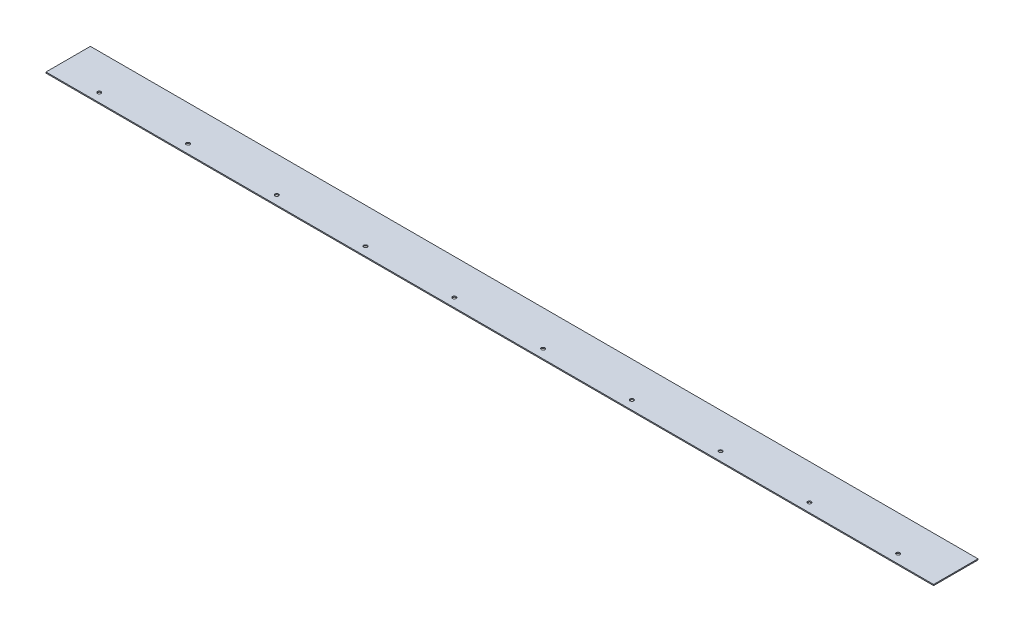
SolidWorks part; units mm, degrees
note: The reader was unsure of these and kept them because the rebuilt part matched: thickness of "Base-Flange1", "Sheet-Metal1", "Sheet-Metal2".
material "Galvanized Steel"
ref_plane "Front Plane" through (0, 0, 0) normal (0, 0, 1) x (1, 0, 0)
ref_plane "Top Plane" through (0, 0, 0) normal (0, 1, 0) x (1, 0, 0)
ref_plane "Right Plane" through (0, 0, 0) normal (1, 0, 0) x (0, 0, -1)
sketch "Sketch1" plane through (0, 0, 0) normal (0, 1, 0) x (1, 0, 0)
  line L1 (-500, -25) -> (500, -25)
  line L2 (-500, -25) -> (-500, 25)
  line L3 (-500, 25) -> (500, 25)
  line L4 (500, -25) -> (500, 25)
  line L5 (-500, -25) -> (500, 25) construction
  line L6 (-500, 25) -> (500, -25) construction
  point P0 (0, 0)
base flange "Base-Flange1" sketch "Sketch1" thickness 1.2 reverse thickness direction no parameters "D1"=2
sketch "Sketch2" plane through (0, 0, 0) normal (0, 1, 0) x (1, 0, 0)
  line L0 (-500, 25) -> (-500, -25) construction
  circle A0 centre (-450, -15) radius 2
  circle A1 centre (-350, -15) radius 2
  circle A2 centre (-250, -15) radius 2
  circle A3 centre (-150, -15) radius 2
  circle A4 centre (-50, -15) radius 2
  circle A5 centre (50, -15) radius 2
  circle A6 centre (150, -15) radius 2
  circle A7 centre (250, -15) radius 2
  circle A8 centre (350, -15) radius 2
  circle A9 centre (450, -15) radius 2
  dimension "D1" = 50
extrude "Cut-Extrude1" cut sketch "Sketch2" against normal blind 10
sketch "Bend-Lines1" [suppressed] plane through (0, 0, 0) normal (0, 1, 0) x (1, 0, 0)
sketch "Bounding-Box1" [suppressed] plane through (0, 0, 0) normal (0, 1, 0) x (1, 0, 0)
sheet metal parameters "Sheet-Metal1" thickness 1.2 parameters "D1"=2
flat pattern "Flat-Pattern1" [suppressed]
sketch "Bend-Lines2" plane through (0, 0, 0) normal (0, 1, 0) x (1, 0, 0)
sketch3d "Bounding-Box2" [suppressed]
  line L0 (-500, 25.75, 0) -> (500, 25.75, 0) construction
  line L1 (-500, -25.75, 0) -> (500, -25.75, 0) construction
  line L2 (-500, 25.75, 0) -> (-500, -25.75, 0) construction
  line L3 (500, 25.75, 0) -> (500, -25.75, 0) construction
sheet metal parameters "Sheet-Metal2" thickness 1.2 parameters "D1"=2, "D7"=0.5
flat pattern "Flat-Pattern1"
sketch "Bend-Lines2" plane through (0, 0, 0) normal (0, 1, 0) x (1, 0, 0)
sketch3d "Bounding-Box2" [suppressed]
  line L0 (500, 25, 0) -> (-500, 25, 0) construction
  line L1 (500, -25, 0) -> (-500, -25, 0) construction
  line L2 (500, 25, 0) -> (500, -25, 0) construction
  line L3 (-500, 25, 0) -> (-500, -25, 0) construction
